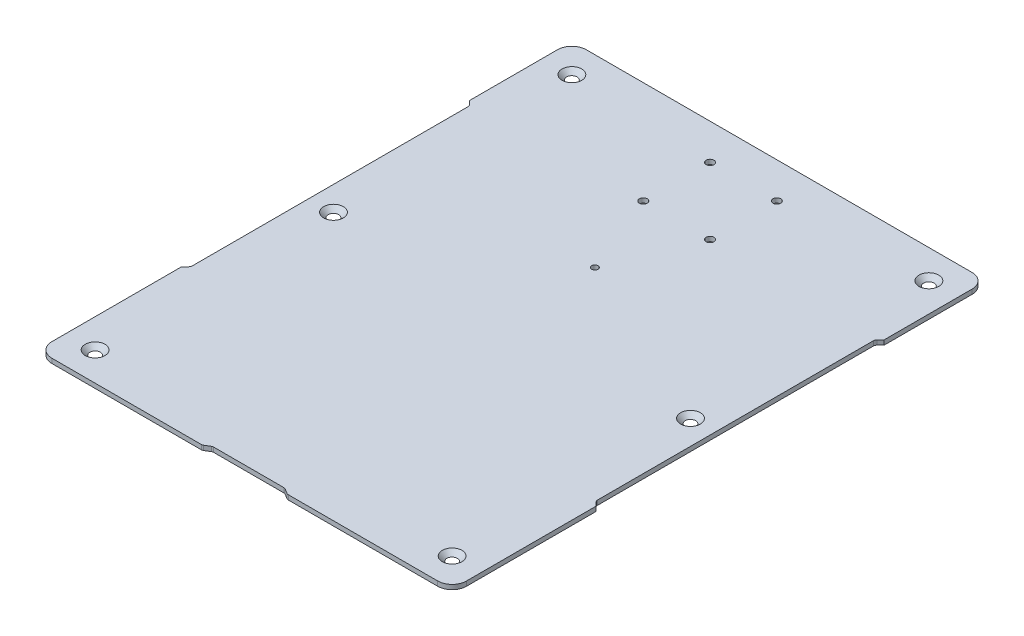
SolidWorks part; units mm, degrees
ref_plane "Front Plane" through (0, 0, 0) normal (0, 0, 1) x (1, 0, 0)
ref_plane "Top Plane" through (0, 0, 0) normal (0, 1, 0) x (1, 0, 0)
ref_plane "Right Plane" through (0, 0, 0) normal (1, 0, 0) x (0, 0, -1)
ref_plane "Plane1" through (0, 30, 0) normal (0, 1, 0) x (1, 0, 0)
sketch "Sketch1" plane through (0, 30, 0) normal (0, 1, 0) x (1, 0, 0)
  line L0 (-180, 232) -> (-180, -232)
  line L1 (-180, -232) -> (180, -232)
  line L2 (180, -232) -> (180, 232)
  line L3 (180, 232) -> (-180, 232)
  line L4 (0, -232) -> (0, 232) construction
  line L5 (-180, 0) -> (180, 0) construction
  line L6 (-155, 207) -> (-155, -232) construction
  circle A0 centre (0, 172) radius 17.5 construction
  circle A1 centre (-155, 207) radius 3.4
  circle A2 centre (155, 207) radius 3.4
  circle A5 centre (-155, -207) radius 3.4
  circle A6 centre (155, -207) radius 3.4
  circle A7 centre (-155, 0) radius 3.4
  circle A8 centre (155, 0) radius 3.4
  circle A9 centre (0, 72) radius 2.731
  point P8 (0, 0)
  point P12 (0, 0)
  dimension "D3" = 35
  dimension "D5" = 6.8
  dimension "D8" = 6.8
  dimension "D1" = 360
  dimension "D2" = 464
  dimension "D4" = 60
  dimension "D6" = 25
  dimension "D7" = 25
  dimension "D9" = 25
  dimension "D11" = 100
  dimension "D12" = 360
extrude "Boss-Extrude1" add sketch "Sketch1" against normal blind 4
fillet "Fillet1" radius 12.5 4 edges at (180, 28, 232) (-180, 28, 232) (180, 28, -232) (-180, 28, -232)
extrude "Cut-Extrude4" cut sketch "Sketch5" against normal blind 20
sketch "Sketch5" plane through (0, 40, 377.3339) normal (0, 1, 0) x (0, 0, 1)
  line L0 (-549.3339, 0) -> (-549.3339, 41) construction
  line L1 (-549.3339, 0) -> (-498.6613, 50.6726) construction
  circle A7 centre (-520.3425, 28.9914) radius 3.4
  circle A8 centre (-520.3425, -28.9914) radius 3.4
  circle A9 centre (-578.3253, -28.9914) radius 3.4
  circle A10 centre (-578.3253, 28.9914) radius 3.4
  point P12 (-549.3339, 0)
  point P13 (-539.2171, 0)
  point P14 (-549.3339, 0)
  point P15 (-514.4105, -0.115)
  point P19 (-549.3339, 0)
  dimension "D3" = 6.8
  dimension "D2" = 45
  dimension "D4" = 41
  dimension "D5" = 4
sketch "Sketch6" plane through (0, 30, 0) normal (0, 1, 0) x (1, 0, 0)
  line L0 (0, 232) -> (0, -232) construction
  line L1 (167.5, 232) -> (-167.5, 232) construction
  line L2 (-167.5, -232) -> (167.5, -232) construction
  line L3 (180, 0) -> (-180, 0) construction
  line L4 (180, -219.5) -> (180, 219.5) construction
  line L5 (-180, 219.5) -> (-180, -219.5) construction
  line L6 (-176, -102.9296) -> (-176, 139.0704)
  line L7 (-176, -102.9296) -> (-188.7279, -115.6575)
  line L8 (-176, 139.0704) -> (-188.7279, 151.7983)
  line L9 (-188.7279, -115.6575) -> (-188.7279, 151.7983)
  point P13 (-124.3469, 2.1706)
  dimension "D1" = 18
  dimension "D2" = 242
  dimension "D3" = 135
  dimension "D4" = 4
extrude "Cut-Extrude5" cut sketch "Sketch6" against normal blind 10
sketch "Sketch7" plane through (0, 30, 0) normal (0, 1, 0) x (1, 0, 0)
  line L0 (0, 232) -> (0, -232) construction
  line L1 (167.5, 232) -> (-167.5, 232) construction
  line L2 (-167.5, -232) -> (167.5, -232) construction
  line L4 (-31.3206, -228.5943) -> (31.3206, -228.5943)
  line L5 (-31.3206, -228.5943) -> (-45, -236.8932)
  line L6 (-45, -236.8932) -> (45, -236.8932)
  line L7 (31.3206, -228.5943) -> (45, -236.8932)
  line L8 (-31.3206, -228.5943) -> (45, -236.8932) construction
  line L9 (-45, -236.8932) -> (31.3206, -228.5943) construction
  dimension "D1" = 90
  dimension "D2" = 16
extrude "Cut-Extrude6" cut sketch "Sketch7" against normal blind 10
ref_plane "Plane2" [suppressed] through (0, 0, 62.9616) normal (0, 0, 1) x (1, 0, 0)
mirror "Mirror2" about plane through (0, 0, 0) normal (1, 0, 0) of "Cut-Extrude5"
fillet "Fillet2" radius 3 8 edges at (-176, 28, 102.9296) (-176, 28, -139.0704) (-36.9344, 28, 232) (-31.3206, 28, 228.5943) (36.9344, 28, 232) (31.3206, 28, 228.5943) (176, 28, 102.9296) (176, 28, -139.0704)
chamfer "Chamfer1" distance 5.15 angle 45 6 edges at (-155, 30, -203.6) (155, 30, 203.6) (155, 30, -3.4) (-155, 30, 210.4) (-155, 30, 3.4) (155, 30, -210.4)
sketch "Sketch9" plane through (0, 30, 0) normal (0, 1, 0) x (1, 0, 0)
  line L0 (0, 232) -> (0, -228.5943) construction
  line L1 (167.5, 232) -> (-167.5, 232) construction
  line L2 (30.4817, -228.5943) -> (-30.4817, -228.5943) construction
  line L3 (-176, 18.0704) -> (176, 18.0704) construction
  line L4 (-176, -101.6869) -> (-176, 137.8278) construction
  line L5 (176, -101.6869) -> (176, 137.8278) construction
  line L6 (-131, 23.0704) -> (-131, -146.9296)
  line L7 (-176, -61.9296) -> (176, -61.9296) construction
  line L8 (-106, 48.0704) -> (106, 48.0704)
  line L9 (-106, -171.9296) -> (106, -171.9296)
  line L10 (131, 23.0704) -> (131, -146.9296)
  arc A0 (-131, -146.9296) -> (-106, -171.9296) centre (-106, -146.9296) ccw
  arc A1 (-131, 23.0704) -> (-106, 48.0704) centre (-106, 23.0704) cw
  arc A2 (131, -146.9296) -> (106, -171.9296) centre (106, -146.9296) cw
  arc A3 (131, 23.0704) -> (106, 48.0704) centre (106, 23.0704) ccw
  point P14 (-131, -61.9296)
  point P21 (-131, -171.9296)
  point P24 (-131, 48.0704)
  point P28 (0, -171.9296)
  point P31 (0, 48.0704)
  dimension "D4" = 25
  dimension "D1" = 45
  dimension "D2" = 80
  dimension "D3" = 220
sketch "Sketch10" [suppressed] plane through (0, 0, 62.9616) normal (0, 0, 1) x (1, 0, 0)
  line L0 (-89.3279, 30) -> (-81.3279, 30)
  line L1 (-144.5624, 30) -> (-37.7732, 30) construction
  arc A0 (-89.3279, 30) -> (-81.3279, 30) centre (-85.3279, 33) ccw
  point P5 (-85.3279, 30)
  dimension "D1" = 10
sweep "Cut-Sweep2" [suppressed] cut profiles "Sketch10" path "Sketch9"
